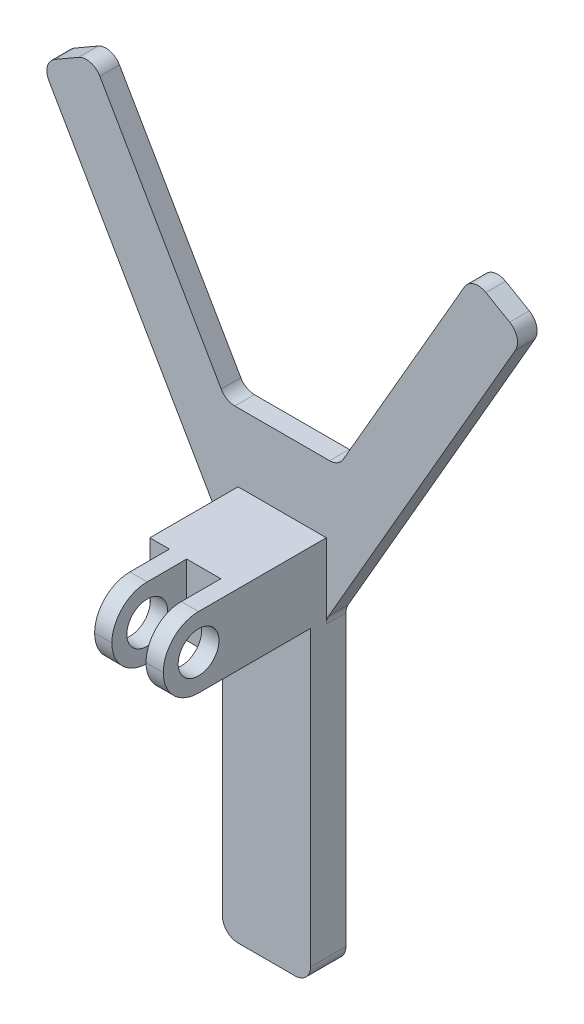
SolidWorks part; units mm, degrees
ref_plane "Plan de face" through (0, 0, 0) normal (0, 0, 1) x (1, 0, 0)
ref_plane "Plan de dessus" through (0, 0, 0) normal (0, 1, 0) x (1, 0, 0)
ref_plane "Plan de droite" through (0, 0, 0) normal (1, 0, 0) x (0, 0, -1)
sketch "Sketch1" plane through (0, 0, 0) normal (0, 0, 1) x (1, 0, 0)
  line L18 (-18.2712, 45) -> (18.2712, 45)
  line L19 (18.2712, 45) -> (61.5725, 120)
  line L20 (61.5725, 120) -> (78.0703, 110.475)
  line L21 (78.0703, 110.475) -> (14.2875, 0)
  line L23 (14.2875, 0) -> (14.2875, -100)
  line L24 (14.2875, -100) -> (-14.2875, -100)
  line L25 (-14.2875, -100) -> (-14.2875, 0)
  line L26 (-14.2875, 0) -> (-78.0703, 110.475)
  line L27 (-78.0703, 110.475) -> (-61.5725, 120)
  line L28 (-61.5725, 120) -> (-18.2712, 45)
  line L29 (-14.2875, 0) -> (14.2875, 0) construction
  point P2 (0, 0)
  point P6 (0, 0)
  point P12 (0, 45)
  point P13 (0, 0)
  point P14 (0, 0)
  dimension "D1" = 28.575
  dimension "D2" = 19.05
  dimension "D3" = 45
  dimension "D4" = 60
  dimension "D5" = 100
  dimension "D6" = 120
extrude "Boss-Extrude1" add sketch "Sketch1" along normal blind 6.35
sketch "Sketch3" plane through (0, 0, 6.35) normal (0, 0, 1) x (1, 0, 0)
  line L0 (0, 45) -> (0, 0) construction
  line L5 (14.2875, 0) -> (-14.2875, 0)
  line L6 (14.2875, 0) -> (14.2875, 22.86)
  line L7 (14.2875, 22.86) -> (-14.2875, 22.86)
  line L8 (-14.2875, 0) -> (-14.2875, 22.86)
  line L9 (14.2875, 0) -> (-14.2875, 22.86) construction
  line L10 (14.2875, 22.86) -> (-14.2875, 0) construction
  line L12 (18.2712, 45) -> (-18.2712, 45) construction
  point P0 (0, 30)
  point P5 (0, 0)
  point P8 (0, 0)
  point P15 (0, 22.5)
  dimension "D1" = 28.575
  dimension "D2" = 22.86
extrude "Boss-Extrude2" add sketch "Sketch3" along normal blind 52.8
sketch "Sketch6" plane through (0, 0, 6.35) normal (0, 0, 1) x (1, 0, 0)
  line L6 (-14.2875, 0) -> (-14.2875, -100) construction
  line L11 (-14.2875, 0) -> (14.2875, 0)
  line L12 (-14.2875, 0) -> (-14.2875, -100)
  line L13 (-14.2875, -100) -> (14.2875, -100)
  line L14 (14.2875, 0) -> (14.2875, -100)
  line L15 (-14.2875, -100) -> (14.2875, -100) construction
  line L16 (14.2875, -100) -> (14.2875, 0) construction
  line L17 (-14.2875, 0) -> (14.2875, 0) construction
extrude "Boss-Extrude3" add sketch "Sketch6" along normal blind 5.08
fillet "Fillet1" radius 5.08 10 edges at (-14.2875, -100, 5.715) (14.2875, -100, 5.715) (78.0703, 110.475, 3.175) (61.5725, 120, 3.175) (-61.5725, 120, 3.175) (-78.0703, 110.475, 3.175) (-18.2712, 45, 3.175) (18.2712, 45, 3.175) (14.2875, 0, 3.175) (-14.2875, 0, 3.175)
sketch "Sketch4" plane through (0, 0, 0) normal (0, -1, 0) x (1, 0, 0)
  line L0 (-14.2875, 59.15) -> (14.2875, 59.15) construction
  line L1 (-14.2875, 59.15) -> (-7.9375, 59.15)
  line L2 (-14.2875, 59.15) -> (-14.2875, 34.925)
  line L3 (-14.2875, 34.925) -> (-7.9375, 34.925)
  line L4 (-7.9375, 59.15) -> (-7.9375, 34.925)
  line L5 (-2.3495, 59.15) -> (8.6995, 59.15)
  line L6 (-2.3495, 59.15) -> (-2.3495, 34.925)
  line L7 (-2.3495, 34.925) -> (8.6995, 34.925)
  line L8 (8.6995, 59.15) -> (8.6995, 34.925)
  line L9 (14.2875, 59.15) -> (14.2875, 11.43) construction
  dimension "D1" = 5.588
  dimension "D2" = 5.588
  dimension "D3" = 24.225
  dimension "D4" = 24.225
  dimension "D5" = 6.35
extrude "Cut-Extrude1" cut sketch "Sketch4" against normal through all
fillet "Fillet3" radius 11.43 4 edges at (11.4935, 22.86, 59.15) (-5.1435, 22.86, 59.15) (11.4935, 0, 59.15) (-5.1435, 0, 59.15)
sketch "Sketch5" plane through (-7.9375, 0, 0) normal (-1, 0, 0) x (0, 0, 1)
  circle A0 centre (47.72, 11.43) radius 6.604
  dimension "D1" = 13.208
extrude "Cut-Extrude2" cut sketch "Sketch5" against normal through all
fillet "Fillet6" [suppressed] radius 2.54
